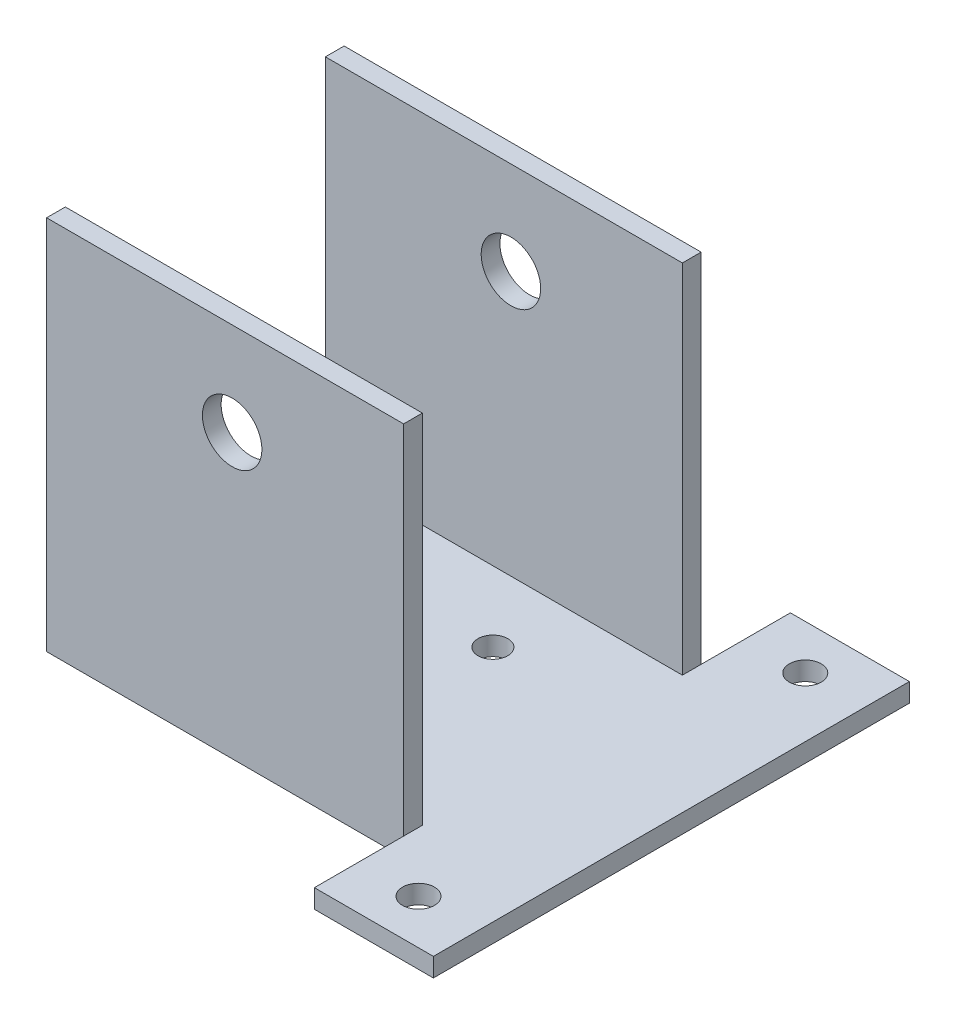
SolidWorks part; units mm, degrees
material "6061 Alloy"
ref_plane "Front Plane" through (0, 0, 0) normal (0, 0, 1) x (1, 0, 0)
ref_plane "Top Plane" through (0, 0, 0) normal (0, 1, 0) x (1, 0, 0)
ref_plane "Right Plane" through (0, 0, 0) normal (1, 0, 0) x (0, 0, -1)
sketch "Sketch1" plane through (0, 0, 0) normal (0, 1, 0) x (1, 0, 0)
  line L0 (-25.4, 15.875) -> (12.7, 15.875)
  line L1 (12.7, 15.875) -> (12.7, 25.4)
  line L2 (12.7, 25.4) -> (25.4, 25.4)
  line L3 (25.4, 25.4) -> (25.4, -25.4)
  line L4 (25.4, -25.4) -> (12.7, -25.4)
  line L5 (12.7, -25.4) -> (12.7, -15.875)
  line L6 (12.7, -15.875) -> (-25.4, -15.875)
  line L7 (-25.4, -15.875) -> (-25.4, 15.875)
  line L8 (19.05, 20.6375) -> (19.05, -20.6375) construction
  line L9 (0, 6.35) -> (0, -6.35) construction
  circle A0 centre (19.05, 20.6375) radius 1.7
  circle A1 centre (19.05, -20.6375) radius 1.7
  circle A2 centre (0, 6.35) radius 1.5875
  circle A3 centre (0, -6.35) radius 1.5875
  point P18 (0, 0)
  dimension "D5" = 3.4
  dimension "D9" = 3.175
  dimension "D1" = 50.8
  dimension "D2" = 50.8
  dimension "D3" = 12.7
  dimension "D4" = 9.525
  dimension "D6" = 41.275
  dimension "D7" = 6.35
  dimension "D8" = 25.4
  dimension "D10" = 12.7
  dimension "D11" = 9.525
  dimension "D12" = 4.7625
  dimension "D13" = 31.75
extrude "Boss-Extrude1" add sketch "Sketch1" along normal blind 2
sketch "Sketch2" plane through (0, 2, 0) normal (0, 1, 0) x (1, 0, 0)
  line L1 (-25.4, 15.875) -> (12.7, 15.875)
  line L2 (-25.4, 15.875) -> (-25.4, 13.875)
  line L3 (-25.4, 13.875) -> (12.7, 13.875)
  line L4 (12.7, 15.875) -> (12.7, 13.875)
  line L5 (-25.4, -15.875) -> (12.7, -15.875)
  line L6 (-25.4, -15.875) -> (-25.4, -13.875)
  line L7 (-25.4, -13.875) -> (12.7, -13.875)
  line L8 (12.7, -15.875) -> (12.7, -13.875)
  dimension "D1" = 2
  dimension "D2" = 2
extrude "Boss-Extrude2" add sketch "Sketch2" along normal blind 38.1
sketch "Sketch3" plane through (0, 0, 15.875) normal (0, 0, 1) x (1, 0, 0)
  line L1 (12.7, 2) -> (25.4, 2) construction
  line L2 (-25.4, 40.1) -> (-25.4, 0) construction
  circle A0 centre (-5.6, 30.168) radius 3.175
  dimension "D1" = 6.35
  dimension "D2" = 28.168
  dimension "D3" = 19.8
extrude "Cut-Extrude1" cut sketch "Sketch3" against normal through all
